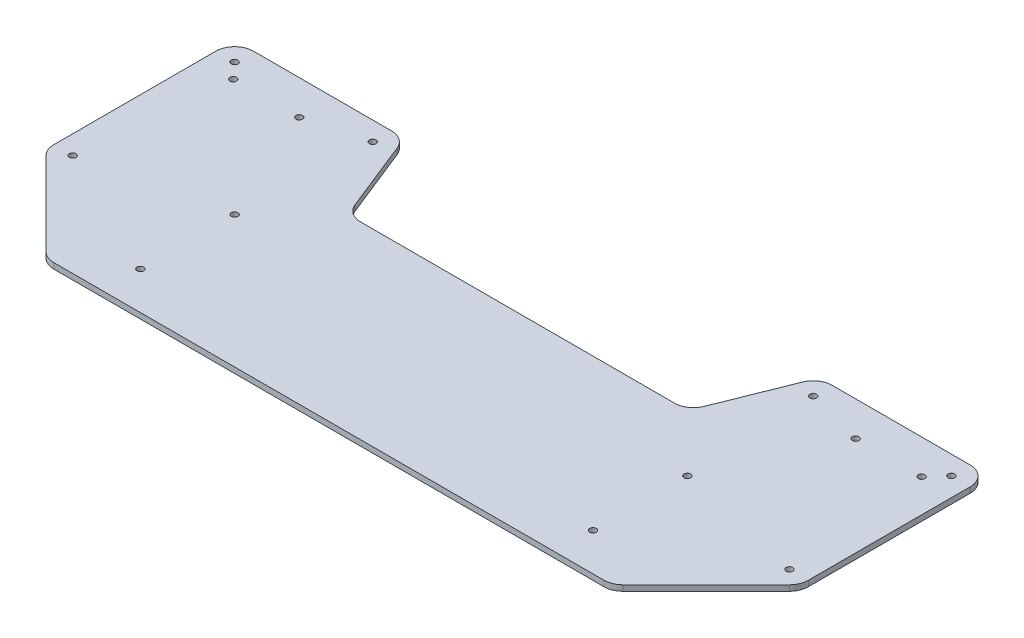
SolidWorks part; units mm, degrees
ref_plane "前视基准面" through (0, 0, 0) normal (0, 0, 1) x (1, 0, 0)
ref_plane "上视基准面" through (0, 0, 0) normal (0, 1, 0) x (1, 0, 0)
ref_plane "右视基准面" through (0, 0, 0) normal (1, 0, 0) x (0, 0, -1)
other "Configuration Table"
sketch "草图1" plane through (0, 0, 0) normal (0, 1, 0) x (1, 0, 0)
  line L0 (-197.0711, -27.9289) -> (-152.9289, -72.0711)
  line L1 (-145.8579, -75) -> (145.8579, -75)
  line L2 (-200, -20.8579) -> (-200, 65)
  line L3 (-190, 75) -> (-116.7703, 75)
  line L4 (200, -20.8579) -> (200, 65)
  line L5 (-200, -75) -> (200, 75) construction
  line L6 (-200, 75) -> (200, -75) construction
  line L7 (152.9289, -72.0711) -> (197.0711, -27.9289)
  line L8 (-107.4856, 68.7139) -> (-92.5144, 31.2861)
  line L9 (-83.2297, 25) -> (83.2297, 25)
  line L10 (107.4856, 68.7139) -> (92.5144, 31.2861)
  line L11 (116.7703, 75) -> (190, 75)
  arc A0 (107.4856, 68.7139) -> (116.7703, 75) centre (116.7703, 65) cw
  arc A1 (92.5144, 31.2861) -> (83.2297, 25) centre (83.2297, 35) cw
  arc A2 (-92.5144, 31.2861) -> (-83.2297, 25) centre (-83.2297, 35) ccw
  arc A3 (-107.4856, 68.7139) -> (-116.7703, 75) centre (-116.7703, 65) ccw
  arc A4 (190, 75) -> (200, 65) centre (190, 65) cw
  arc A5 (-200, 65) -> (-190, 75) centre (-190, 65) cw
  arc A6 (197.0711, -27.9289) -> (200, -20.8579) centre (190, -20.8579) ccw
  arc A7 (152.9289, -72.0711) -> (145.8579, -75) centre (145.8579, -65) cw
  arc A8 (-197.0711, -27.9289) -> (-200, -20.8579) centre (-190, -20.8579) cw
  arc A9 (-152.9289, -72.0711) -> (-145.8579, -75) centre (-145.8579, -65) ccw
  point P0 (0, 0)
  point P14 (0, 25)
  dimension "D4" = 10
  dimension "D5" = 10
  dimension "D1" = 400
  dimension "D2" = 150
  dimension "D3" = 50
extrude "凸台-拉伸1" add sketch "草图1" along normal blind 3
sketch "草图2" plane through (0, 0, 0) normal (0, -1, 0) x (1, 0, 0)
  line L0 (0, 0) -> (0, 50000) construction
  circle A0 centre (120, 5) radius 1.75
  circle A1 centre (120, 55) radius 1.75
  circle A2 centre (-120, 55) radius 1.75
  circle A3 centre (-120, 5) radius 1.75
extrude "切除-拉伸1" cut sketch "草图2" against normal blind 59
sketch "草图3" plane through (0, 3, 0) normal (0, 1, 0) x (1, 0, 0)
  line L0 (0, 0) -> (0, 50000) construction
  circle A0 centre (116.7703, 65) radius 1.75
  circle A1 centre (190, 65) radius 1.75
  circle A2 centre (-190, 65) radius 1.75
  circle A3 centre (-116.7703, 65) radius 1.75
  circle A4 centre (-190, -20.8579) radius 1.75
  circle A5 centre (190, -20.8579) radius 1.75
  dimension "D1" = 3.5
  dimension "D2" = 3.5
  dimension "D3" = 3.5
extrude "切除-拉伸2" cut sketch "草图3" against normal blind 59
sketch "草图4" plane through (0, 0, 0) normal (0, -1, 0) x (1, 0, 0)
  line L2 (0, 0) -> (0, -50000) construction
  line L3 (-1137.5, -55) -> (0, -55) construction
  line L4 (137.5, -48) -> (137.5, -62) construction
  line L5 (192.5, -62) -> (192.5, -48) construction
  line L6 (182.5, -55) -> (182.5, -65) construction
  line L8 (175.5, -65) -> (189.5, -65) construction
  line L9 (147.5, -55) -> (147.5, -65) construction
  line L11 (140.5, -65) -> (154.5, -65) construction
  line L12 (147.5, -55) -> (182.5, -55) construction
  circle A0 centre (147.5, -56.75) radius 1.75
  circle A1 centre (182.5, -56.75) radius 1.75
  circle A2 centre (-182.5, -56.75) radius 1.75
  circle A3 centre (-147.5, -56.75) radius 1.75
  point P15 (137.5, -55)
  point P18 (192.5, -55)
  point P21 (147.5, -55)
  point P22 (182.5, -55)
  point P25 (147.5, -56.75)
  point P27 (182.5, -56.75)
  dimension "D1" = 3.5
  dimension "D2" = 3.5
extrude "切除-拉伸3" cut sketch "草图4" against normal blind 59
